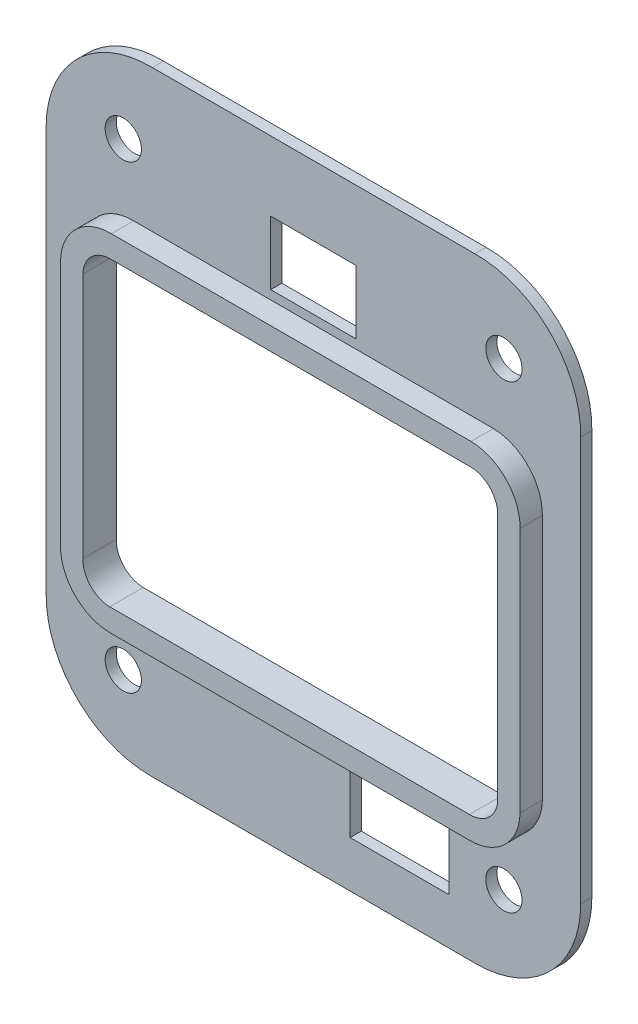
SolidWorks part; units mm, degrees
ref_plane "前视基准面" through (0, 0, 0) normal (0, 0, 1) x (1, 0, 0)
ref_plane "上视基准面" through (0, 0, 0) normal (0, 1, 0) x (1, 0, 0)
ref_plane "右视基准面" through (0, 0, 0) normal (1, 0, 0) x (0, 0, -1)
sketch "Model" plane through (0, 0, 0) normal (0, 0, 1) x (1, 0, 0)
  line L0 (79.502, 73.533) -> (79.502, 95.631)
  line L1 (82.042, 98.044) -> (114.3, 98.044)
  line L2 (81.915, 70.993) -> (114.173, 70.993)
  line L3 (116.713, 73.406) -> (116.713, 95.5042)
  line L4 (122.1533, 67.0595) -> (122.1533, 103.2945)
  line L5 (74.2112, 67.1865) -> (74.2112, 103.4322)
  line L6 (83.7432, 112.7877) -> (112.6602, 112.7877)
  line L7 (83.5782, 57.6934) -> (112.7872, 57.6934)
  line L8 (93.853, 106.553) -> (94.615, 106.553)
  line L9 (94.615, 106.553) -> (102.489, 106.553)
  line L10 (93.853, 101.346) -> (93.853, 106.553)
  line L11 (93.853, 101.346) -> (102.489, 101.346)
  line L12 (102.489, 101.346) -> (102.489, 106.553)
  line L13 (101.473, 67.945) -> (110.363, 67.945)
  line L14 (110.363, 61.849) -> (110.363, 67.945)
  line L15 (101.473, 61.849) -> (110.363, 61.849)
  line L16 (101.473, 61.849) -> (101.473, 67.945)
  line L17 (77.502, 73.5549) -> (77.502, 95.6529)
  line L18 (82.0639, 100.044) -> (114.3219, 100.044)
  line L19 (118.713, 73.3841) -> (118.713, 95.4824)
  line L20 (81.8931, 68.993) -> (114.1511, 68.993)
  arc A0 (82.0639, 100.044) -> (77.502, 95.6529) centre (81.9785, 95.5675) ccw
  arc A1 (118.713, 95.4824) -> (114.3219, 100.044) centre (114.2365, 95.5675) ccw
  arc A2 (114.1511, 68.993) -> (118.713, 73.3841) centre (114.2365, 73.4695) ccw
  arc A3 (77.502, 73.5549) -> (81.8931, 68.993) centre (81.9785, 73.4695) ccw
  arc A34 (114.173, 70.993) -> (116.713, 73.406) centre (114.2365, 73.4695) ccw
  arc A37 (79.502, 73.533) -> (81.915, 70.993) centre (81.9785, 73.4695) ccw
  arc A40 (116.713, 95.5042) -> (114.3, 98.044) centre (114.2365, 95.5675) ccw
  arc A43 (82.042, 98.044) -> (79.502, 95.631) centre (81.9785, 95.5675) ccw
  circle A46 centre (81.1272, 105.9434) radius 1.626
  circle A49 centre (115.2648, 105.9434) radius 1.626
  circle A52 centre (81.1272, 64.6938) radius 1.626
  arc A55 (74.2112, 67.1865) -> (83.5782, 57.6934) centre (83.5774, 67.0604) ccw
  arc A58 (83.7432, 112.7877) -> (74.2112, 103.4322) centre (83.5772, 103.4231) ccw
  arc A61 (112.7872, 57.6934) -> (122.1533, 67.0595) centre (112.7873, 67.0594) ccw
  arc A64 (122.1533, 103.2945) -> (112.6602, 112.7877) centre (112.7872, 103.4215) ccw
  circle A67 centre (115.2648, 64.6938) radius 1.626
  dimension "D1" = 2
extrude "凸台-拉伸1" add sketch "Model" along normal blind 1 contours L4 A64 L6 A58 L5 A55 L7 A61 A67 L15 L16 L13 L14 L12 L11 L10 L8 L9 A3 L17 A0 L18 A1 L19 A2 L20 A46 A49 A52 region at (118.8937, 60.9531, 0)
extrude "凸台-拉伸2" add sketch "Model<3>" along normal blind 3 contours L17 A3 L20 A2 L19 A1 L18 A0 A43 L1 A40 L3 A34 L2 A37 L0 region at (78.018, 84.6039, 0)
sketch "Model<3>" plane through (0, 0, 0) normal (0, 0, 1) x (1, 0, 0) same geometry as "Model"
sketch "草图1" plane through (0, 67.945, 0) normal (0, -1, 0) x (1, 0, 0)
  line L1 (101.473, 1) -> (110.363, 1)
  line L2 (101.473, 1) -> (101.473, 0)
  line L3 (101.473, 0) -> (110.363, 0)
  line L4 (110.363, 1) -> (110.363, 0)
extrude "凸台-拉伸3" add sketch "草图1" along normal blind 0.5
sketch "草图2" plane through (93.853, 0, 0) normal (1, 0, 0) x (0, 0, -1)
  line L1 (-1, 106.553) -> (0, 106.553)
  line L2 (-1, 106.553) -> (-1, 101.346)
  line L3 (-1, 101.346) -> (0, 101.346)
  line L4 (0, 106.553) -> (0, 101.346)
extrude "凸台-拉伸4" add sketch "草图2" along normal blind 0.5
sketch "草图3" plane through (102.489, 0, 0) normal (-1, 0, 0) x (0, 0, 1)
  line L1 (0, 106.553) -> (1, 106.553)
  line L2 (0, 106.553) -> (0, 101.346)
  line L3 (0, 101.346) -> (1, 101.346)
  line L4 (1, 106.553) -> (1, 101.346)
extrude "凸台-拉伸5" add sketch "草图3" along normal blind 0.5
sketch "草图4" plane through (0, 101.346, 0) normal (0, 1, 0) x (1, 0, 0)
  line L1 (94.353, 0) -> (101.989, 0)
  line L2 (94.353, 0) -> (94.353, -1)
  line L3 (94.353, -1) -> (101.989, -1)
  line L4 (101.989, 0) -> (101.989, -1)
extrude "切除-拉伸1" cut sketch "草图4" against normal blind 0.5
